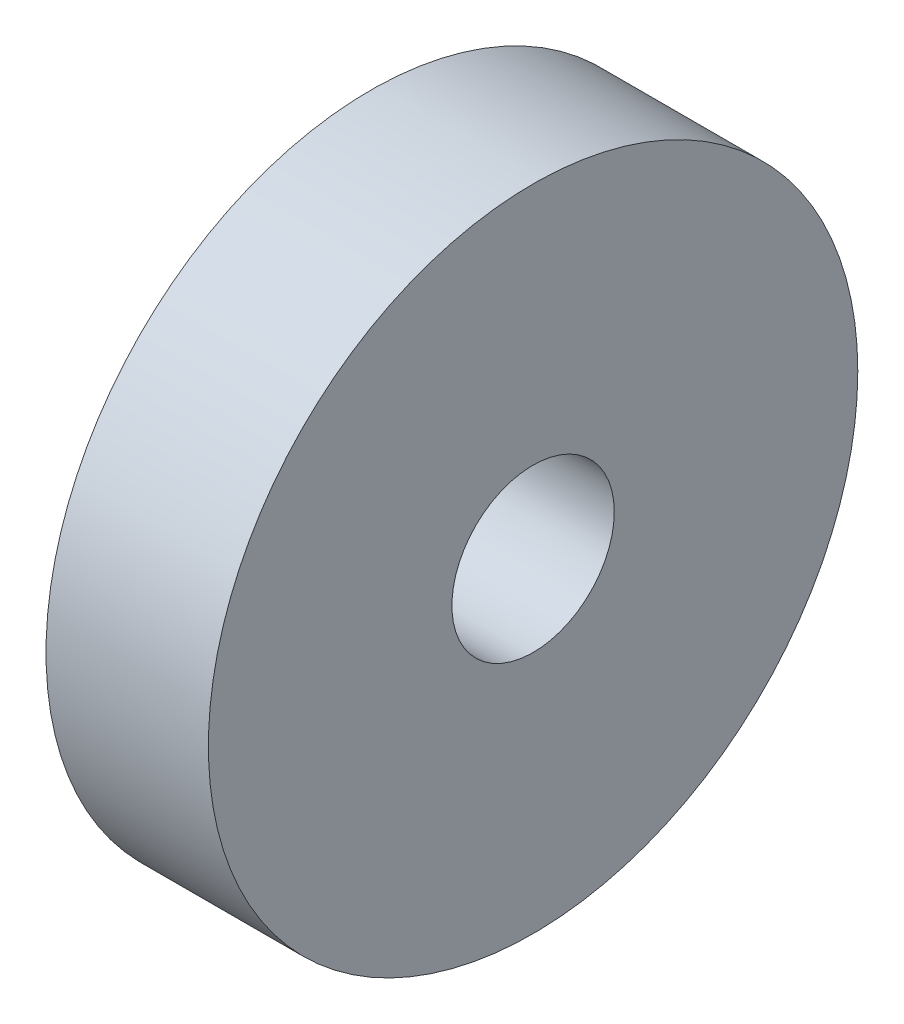
SolidWorks part; units mm, degrees
material "ABS"
ref_plane "Спереди" through (0, 0, 0) normal (0, 0, 1) x (1, 0, 0)
ref_plane "Сверху" through (0, 0, 0) normal (0, 1, 0) x (1, 0, 0)
ref_plane "Справа" through (0, 0, 0) normal (1, 0, 0) x (0, 0, -1)
sketch "Эскиз1" plane through (0, 0, 0) normal (1, 0, 0) x (0, 0, -1)
  circle A0 centre (0, 0) radius 100
  circle A1 centre (0, 0) radius 25
  dimension "D1" = 200
  dimension "D2" = 50
extrude "Бобышка-Вытянуть1" add sketch "Эскиз1" along normal blind 25 and the other way blind 25
